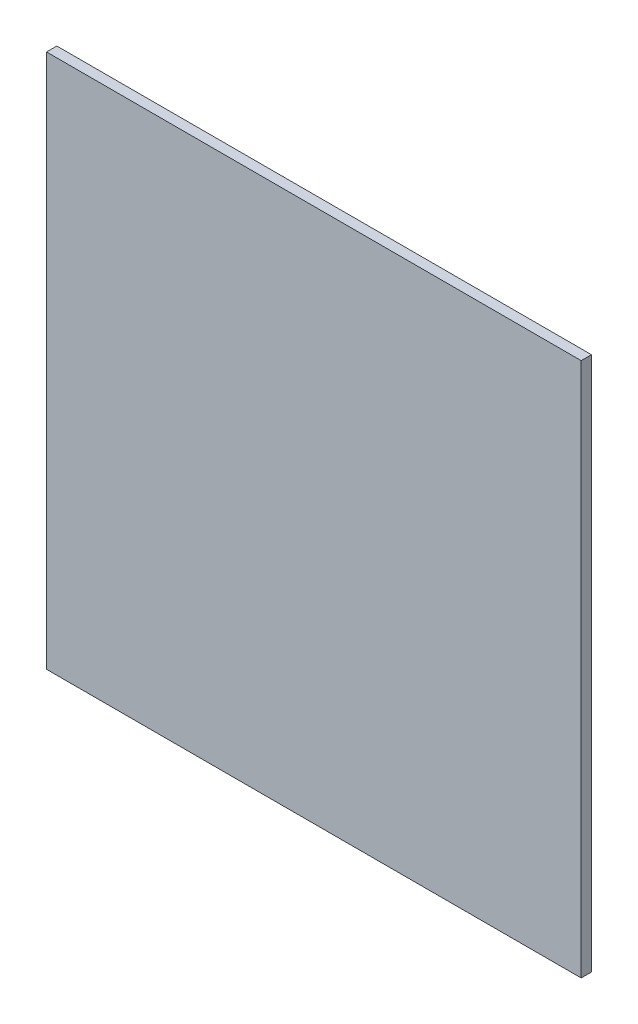
SolidWorks part; units mm, degrees
material "ALUMINUM 6061-T6"
ref_plane "Front Plane" through (0, 0, 0) normal (0, 0, 1) x (1, 0, 0)
ref_plane "Top Plane" through (0, 0, 0) normal (0, 1, 0) x (1, 0, 0)
ref_plane "Right Plane" through (0, 0, 0) normal (1, 0, 0) x (0, 0, -1)
sketch "Sketch1" plane through (0, 0, 0) normal (0, 0, 1) x (1, 0, 0)
  line L1 (-165.1, -165.1) -> (165.1, -165.1)
  line L2 (-165.1, -165.1) -> (-165.1, 165.1)
  line L3 (-165.1, 165.1) -> (165.1, 165.1)
  line L4 (165.1, -165.1) -> (165.1, 165.1)
  line L5 (-165.1, -165.1) -> (165.1, 165.1) construction
  line L6 (-165.1, 165.1) -> (165.1, -165.1) construction
  point P0 (0, 0)
  dimension "D1" = 330.2
  dimension "D2" = 330.2
extrude "Boss-Extrude1" add sketch "Sketch1" along normal mid plane 6.35
